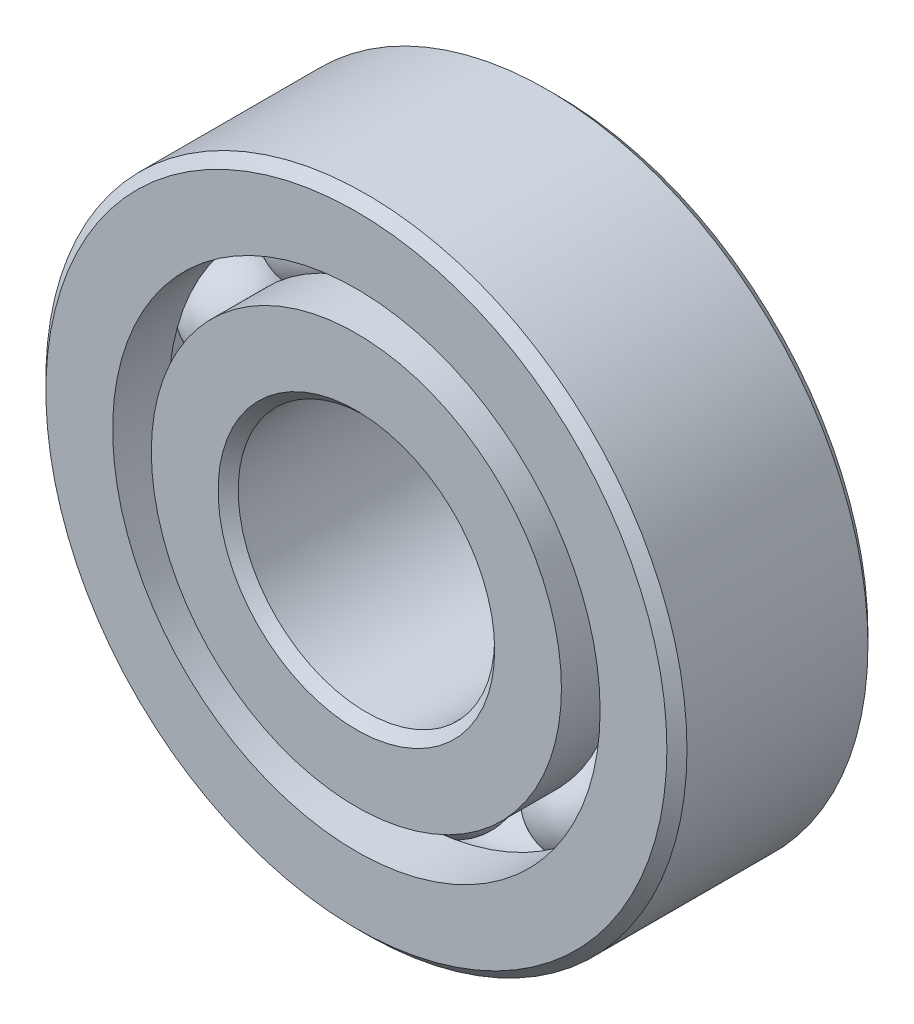
SolidWorks part; units mm, degrees
ref_plane "Front Plane" through (0, 0, 0) normal (0, 0, 1) x (1, 0, 0)
ref_plane "Top Plane" through (0, 0, 0) normal (0, 1, 0) x (1, 0, 0)
ref_plane "Right Plane" through (0, 0, 0) normal (1, 0, 0) x (0, 0, -1)
sketch "Sketch1" plane through (0, 0, 0) normal (1, 0, 0) x (0, 0, -1)
  line L0 (-2.4892, 0) -> (2.4892, 0) construction
  line L1 (0, 7.9375) -> (0, -7.9375) construction
  line L2 (2.2403, 7.9375) -> (-2.2403, 7.9375)
  line L3 (-2.2403, 7.9375) -> (-2.4892, 7.6886)
  line L4 (-2.4892, 7.6886) -> (-2.4892, 6.0352)
  line L5 (-2.4892, 6.0352) -> (-1.1063, 6.0352)
  line L6 (2.4892, 6.0352) -> (1.1063, 6.0352)
  line L7 (2.4892, 7.6886) -> (2.4892, 6.0352)
  line L8 (2.2403, 7.9375) -> (2.4892, 7.6886)
  line L9 (0, 7.9375) -> (0, 5.5562) construction
  line L10 (0, 5.5562) -> (0, 3.175) construction
  arc A0 (-1.1063, 6.0352) -> (1.1063, 6.0352) centre (0, 5.5562) cw
  point P14 (0, 3.175)
  dimension "D3" = 2.2126
  dimension "D1" = 45
  dimension "Width" = 4.9784
  dimension "OD" = 15.875
  dimension "D2" = 0.2489
  dimension "Shaft Dia" = 6.35
  dimension "D4" = 0.479
revolve "Revolve1" add sketch "Sketch1" angle 360 about L0
sketch "Sketch3" plane through (0, 0, 0) normal (1, 0, 0) x (0, 0, -1)
  line L0 (-2.4892, 5.0773) -> (-1.1063, 5.0773)
  line L1 (0, 7.9375) -> (0, -7.9375) construction
  line L2 (-2.4892, 7.6886) -> (-2.4892, 6.0352) construction
  line L3 (-2.4892, 5.0773) -> (-2.4892, 3.4239)
  line L4 (-2.2403, 7.9375) -> (-2.4892, 7.6886) construction
  line L5 (-2.4892, 3.4239) -> (-2.2403, 3.175)
  line L6 (-2.2403, 3.175) -> (2.2403, 3.175)
  line L7 (2.2403, 7.9375) -> (2.2403, -7.9375) construction
  line L8 (2.2403, 3.175) -> (2.4892, 3.4239)
  line L9 (2.4892, -7.6886) -> (2.4892, 7.6886) construction
  line L10 (2.4892, 3.4239) -> (2.4892, 5.0773)
  line L11 (2.4892, 5.0773) -> (1.1063, 5.0773)
  line L13 (2.2403, 7.9375) -> (2.4892, 7.6886) construction
  arc A0 (1.1063, 6.0352) -> (-1.1063, 6.0352) centre (0, 5.5562) ccw construction
  arc A1 (1.1063, 5.0773) -> (-1.1063, 5.0773) centre (0, 5.5563) cw
revolve "Revolve3" add sketch "Sketch3" angle 360 about L0
sketch "Sketch4" plane through (0, 0, 0) normal (1, 0, 0) x (0, 0, -1)
  line L0 (-1.2055, 5.5562) -> (1.2055, 5.5562)
  arc A2 (-1.2055, 5.5562) -> (1.2055, 5.5562) centre (0, 5.5562) cw
  arc A3 (1.1063, 6.0352) -> (-1.1063, 6.0352) centre (0, 5.5562) ccw construction
revolve "Revolve4" add sketch "Sketch4" angle 360 about L0
ref_axis "Axis1" through (0, 0, -2.4892) along (0, 0, 1)
pattern_circular "CirPattern1" count 10 every 36 about axis through (0, 0, -2.4892) along (0, 0, 1) of bodies 104
equation "\"D2@Sketch1\" = \"Width@Sketch1\"*.05"
equation "\"D3@Sketch1\" = \"Width@Sketch1\"/2.25"
equation "\"D4@Sketch1\" = (((\"OD@Sketch1\"-\"Width@Sketch1\")/2)/3.25)/3.5"
equation "\"D2@CirPattern1\" = 360/\"Balls@CirPattern1\""
